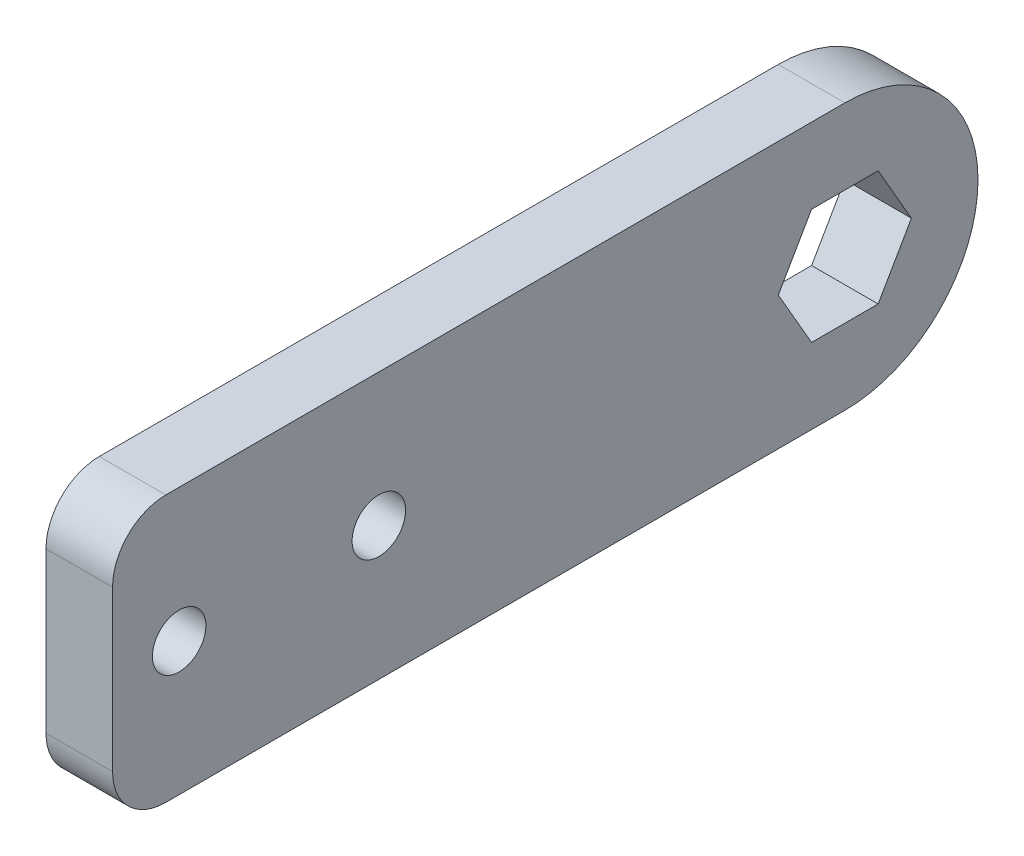
SolidWorks part; units mm, degrees
material "5052-O"
ref_plane "Front Plane" through (0, 0, 0) normal (0, 0, 1) x (1, 0, 0)
ref_plane "Top Plane" through (0, 0, 0) normal (0, 1, 0) x (1, 0, 0)
ref_plane "Right Plane" through (0, 0, 0) normal (1, 0, 0) x (0, 0, -1)
sketch "Sketch1" plane through (0, 0, 0) normal (1, 0, 0) x (0, 0, -1)
  line L1 (-41.275, -12.7) -> (41.275, -12.7)
  line L2 (-41.275, -12.7) -> (-41.275, 12.7)
  line L3 (-41.275, 12.7) -> (41.275, 12.7)
  line L4 (41.275, -12.7) -> (41.275, 12.7)
  line L5 (-41.275, -12.7) -> (41.275, 12.7) construction
  line L6 (-41.275, 12.7) -> (41.275, -12.7) construction
  point P0 (0, 0)
  dimension "D1" = 25.4
  dimension "D2" = 82.55
extrude "Boss-Extrude1" add sketch "Sketch1" along normal mid plane 6.35
fillet "Fillet1" radius 12.7 2 edges at (0, -12.7, -41.275) (0, 12.7, -41.275)
hole_wizard "#10 Clearance Hole1" positions "Sketch3" profile "Sketch5" hole size "#10" standard "ANSI Inch" end condition through all
sketch "Sketch3" plane through (3.175, 6.2729, 168.827) normal (1, 0, 0) x (0, 0, -1)
  line L0 (127.552, 6.4271) -> (127.552, -18.9729) construction
  point P0 (152.952, -6.2729)
  point P3 (133.902, -6.2729)
  point P8 (127.552, -6.2729)
  dimension "D1" = 19.05
  dimension "D2" = 6.35
sketch "Sketch5" plane through (3.175, 0, 15.875) normal (0, 1, 0) x (0, 0, -1)
  line L0 (0, 0) -> (0, 6.35)
  line L1 (0, 6.35) -> (2.5527, 6.35)
  line L2 (2.5527, 6.35) -> (2.5527, 0)
  line L5 (2.5527, 0) -> (0, 0)
  line L11 (0, -6.35) -> (0, 107.95) construction
  dimension "Thru Hole Dia." = 5.1054
  dimension "Thru Hole Depth" = 6.35
fillet "Fillet2" radius 5.08 2 edges at (0, -12.7, 41.275) (0, 12.7, 41.275)
sketch "Sketch7" plane through (3.175, 0, 0) normal (1, 0, 0) x (0, 0, -1)
  line L1 (31.75, 5.4993) -> (25.4, 5.4993)
  line L2 (25.4, 5.4993) -> (22.225, 0)
  line L3 (22.225, 0) -> (25.4, -5.4993)
  line L4 (25.4, -5.4993) -> (31.75, -5.4993)
  line L5 (31.75, -5.4993) -> (34.925, 0)
  line L6 (34.925, 0) -> (31.75, 5.4993)
  circle A1 centre (28.575, 0) radius 5.4993 construction
  arc A3 (41.275, 0) -> (28.575, 12.7) centre (28.575, 0) ccw construction
  point P1 (0, 0)
  point P10 (0, 0)
  dimension "D1" = 12.7
extrude "Cut-Extrude1" cut sketch "Sketch7" against normal through all
